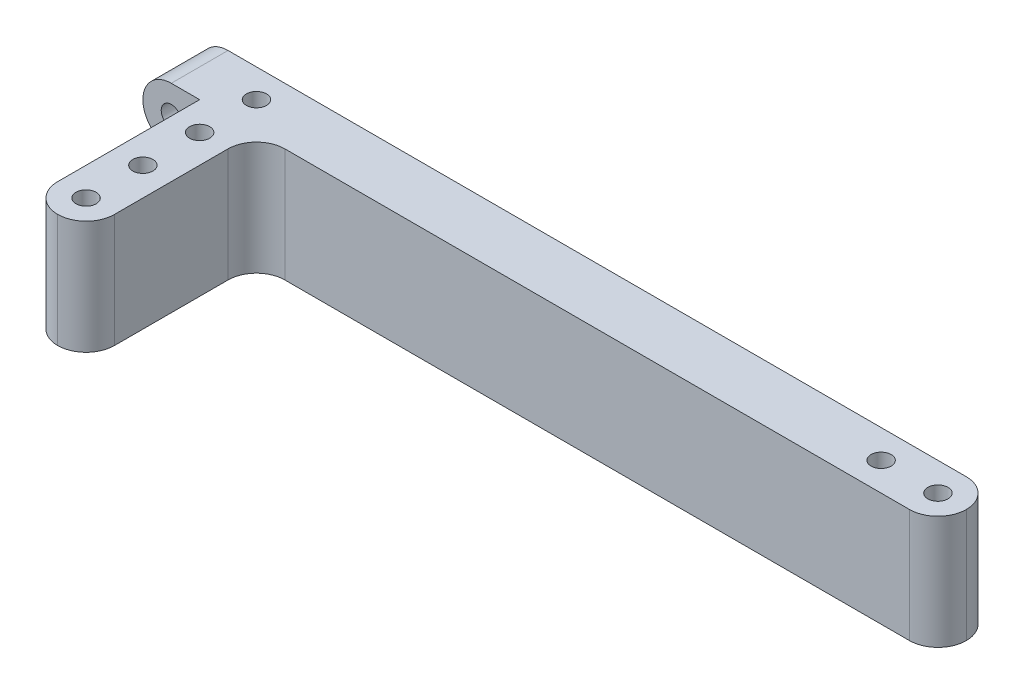
SolidWorks part; units mm, degrees
ref_plane "Front Plane" through (0, 0, 0) normal (0, 0, 1) x (1, 0, 0)
ref_plane "Top Plane" through (0, 0, 0) normal (0, 1, 0) x (1, 0, 0)
ref_plane "Right Plane" through (0, 0, 0) normal (1, 0, 0) x (0, 0, -1)
sketch "Sketch1" plane through (0, 0, 0) normal (0, 1, 0) x (1, 0, 0)
  line L0 (0, 0) -> (0, 38.1) construction
  line L1 (0, 38.1) -> (152.4, 38.1) construction
  line L2 (158.75, 44.45) -> (158.75, 31.75)
  line L3 (158.75, 31.75) -> (6.35, 31.75)
  line L4 (6.35, 31.75) -> (6.35, -6.35)
  line L5 (6.35, -6.35) -> (-6.35, -6.35)
  line L6 (-6.35, -6.35) -> (-6.35, 31.75)
  line L7 (-6.35, 31.75) -> (-19.05, 31.75)
  line L8 (-19.05, 31.75) -> (-19.05, 44.45)
  line L9 (-19.05, 44.45) -> (158.75, 44.45)
  circle A0 centre (0, 38.1) radius 2.25
  circle A1 centre (152.4, 38.1) radius 2.25
  circle A2 centre (139.7, 38.1) radius 2.25
  circle A3 centre (0, 25.4) radius 2.25
  circle A4 centre (0, 12.7) radius 2.25
  circle A5 centre (0, 0) radius 2.25
  point P16 (0, 0)
  dimension "D3" = 4.5
  dimension "D1" = 38.1
  dimension "D2" = 152.4
  dimension "D4" = 12.7
  dimension "D6" = 12.7
  dimension "D7" = 12.7
  dimension "D8" = 12.7
  dimension "D9" = 6.35
  dimension "D10" = 6.35
  dimension "D5" = 4
extrude "Boss-Extrude1" add sketch "Sketch1" along normal blind 25.4
sketch "Sketch2" plane through (0, 0, -31.75) normal (0, 0, 1) x (1, 0, 0)
  line L10 (-19.05, 25.4) -> (-6.35, 25.4) construction
  line L11 (-19.05, 25.4) -> (-19.05, 0) construction
  line L12 (-6.35, 25.4) -> (-6.35, 0) construction
  line L13 (-19.05, 0) -> (-6.35, 0)
  line L14 (-19.05, 0) -> (-19.05, 12.7)
  line L15 (-19.05, 12.7) -> (-6.35, 12.7)
  line L16 (-6.35, 0) -> (-6.35, 12.7)
  circle A0 centre (-12.7, 19.05) radius 2.25
  dimension "D1" = 4.5
  dimension "D2" = 6.35
  dimension "D3" = 6.35
  dimension "D4" = 12.7
extrude "Cut-Extrude1" cut sketch "Sketch2" against normal blind 12.7
fillet "Fillet1" radius 6.35 8 edges at (158.75, 12.7, -44.45) (158.75, 12.7, -31.75) (6.35, 12.7, 6.35) (-6.35, 12.7, 6.35) (-6.35, 6.35, -44.45) (6.35, 12.7, -31.75) (-19.05, 12.7, -38.1) (-19.05, 25.4, -38.1)
fillet "Fillet2" radius 6.35 2 edges at (-4.4901, 12.7, -42.5901) (-6.35, 12.7, -34.925)
